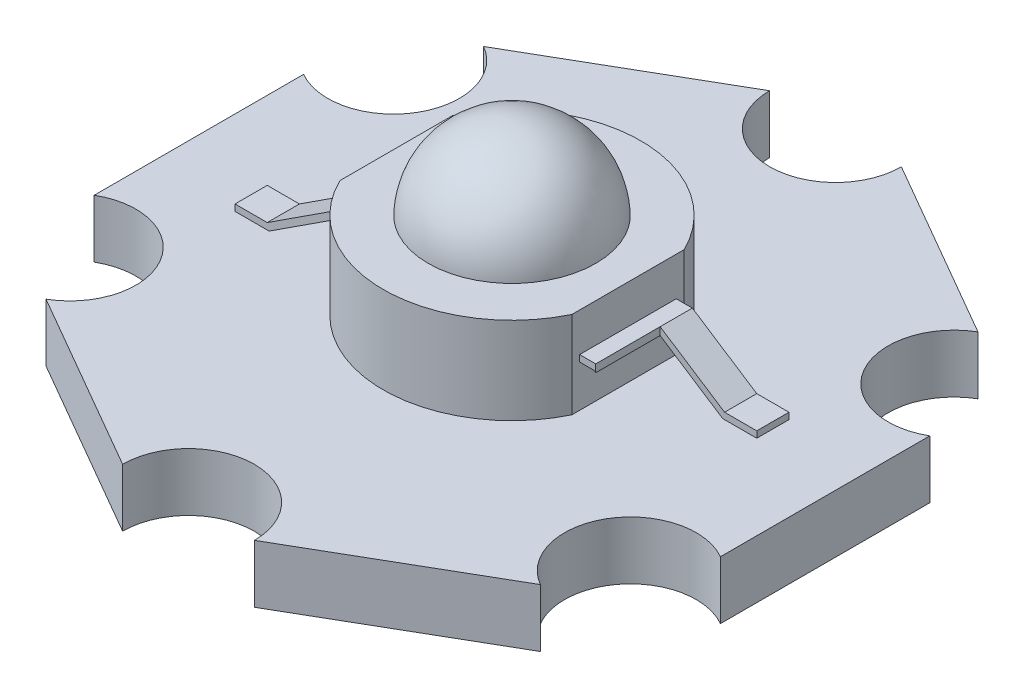
SolidWorks part; units mm, degrees
ref_plane "Front Plane" through (0, 0, 0) normal (0, 0, 1) x (1, 0, 0)
ref_plane "Top Plane" through (0, 0, 0) normal (0, 1, 0) x (1, 0, 0)
ref_plane "Right Plane" through (0, 0, 0) normal (1, 0, 0) x (0, 0, -1)
sketch "Sketch1" plane through (0, 0, 0) normal (0, 1, 0) x (1, 0, 0)
  line L0 (-10.25, 0) -> (0, 0) construction
  line L1 (0, 0) -> (10.25, 0) construction
  line L2 (-9.7211, 3.25) -> (-9.7211, 0)
  line L3 (-9.7211, 0) -> (-9.7211, -3.25)
  line L4 (0, 0) -> (0, 10.25) construction
  line L5 (0, 0) -> (0, -10.25) construction
  line L6 (-4.8606, 8.4187) -> (-7.6751, 6.7937)
  line L7 (-2.046, 10.0437) -> (-4.8606, 8.4187)
  line L8 (4.8606, 8.4187) -> (2.046, 10.0437)
  line L9 (7.6751, 6.7937) -> (4.8606, 8.4187)
  line L10 (9.7211, 0) -> (9.7211, 3.25)
  line L11 (9.7211, -3.25) -> (9.7211, 0)
  line L12 (4.8606, -8.4187) -> (7.6751, -6.7937)
  line L13 (2.046, -10.0437) -> (4.8606, -8.4187)
  line L14 (-4.8606, -8.4187) -> (-2.046, -10.0437)
  line L15 (-7.6751, -6.7937) -> (-4.8606, -8.4187)
  circle A0 centre (0, 0) radius 10.25 construction
  circle A1 centre (0, 0) radius 8 construction
  arc A2 (-9.7211, 3.25) -> (-7.6751, 6.7937) centre (-8.7001, 5.023) ccw
  arc A3 (-2.046, 10.0437) -> (2.046, 10.0437) centre (0, 10.046) ccw
  arc A4 (7.6751, 6.7937) -> (9.7211, 3.25) centre (8.7001, 5.023) ccw
  arc A5 (9.7211, -3.25) -> (7.6751, -6.7937) centre (8.7001, -5.023) ccw
  arc A6 (2.046, -10.0437) -> (-2.046, -10.0437) centre (0, -10.046) ccw
  arc A7 (-7.6751, -6.7937) -> (-9.7211, -3.25) centre (-8.7001, -5.023) ccw
  point P28 (0, 0)
  point P46 (0, 0)
  dimension "D1" = 20.5
  dimension "D2" = 16
  dimension "D3" = 6.5
  dimension "D4" = 6
  dimension "D5" = 6
extrude "Boss-Extrude1" add sketch "Sketch1" along normal blind 1.8
sketch "Sketch2" plane through (0, 1.8, 0) normal (0, 1, 0) x (1, 0, 0)
  circle A0 centre (0, 0) radius 4
  dimension "D1" = 8
extrude "Boss-Extrude2" add sketch "Sketch2" along normal blind 2.7
sketch "Sketch3" plane through (0, 4.5, 0) normal (0, 1, 0) x (1, 0, 0)
  line L0 (-3.6, 5.0619) -> (-3.6, -4.9568)
  line L1 (-3.6, -4.9568) -> (3.6, -4.9568)
  line L2 (3.6, -4.9568) -> (3.6, 5.2871)
  line L3 (3.6, 5.2871) -> (4.7694, 5.2871)
  line L4 (4.7694, 5.2871) -> (4.7694, -6.0544)
  line L5 (4.7694, -6.0544) -> (-4.6413, -6.0544)
  line L6 (-4.6413, -6.0544) -> (-4.6413, 5.0619)
  line L7 (-4.6413, 5.0619) -> (-3.6, 5.0619)
  line L8 (0, 0) -> (3.6, 0) construction
  line L9 (0, 0) -> (-3.6, 0) construction
  dimension "D1" = 7.2
extrude "Cut-Extrude1" cut sketch "Sketch3" against normal up to surface (2.7 mm away) up to face at (0, 1.8, 4)
sketch "Sketch4" plane through (0, 0, 0) normal (1, 0, 0) x (0, 0, -1)
  line L0 (0, 0) -> (0, 10.0744) construction
  line L1 (0, 7) -> (0, 4.5)
  line L2 (1.7436, 4.5) -> (-1.7436, 4.5) construction
  line L3 (0, 4.5) -> (2.6, 4.5)
  line L4 (4, 4.5) -> (1.7436, 4.5) construction
  line L5 (0, 7) -> (-1.2549, 7) construction
  arc A0 (0, 7) -> (2.6, 4.5) centre (0, 4.398) cw
  dimension "D2" = 7
  dimension "D1" = 5.2
revolve "Revolve1" add sketch "Sketch4" angle 360 about L0
sketch "Sketch5" plane through (0, 0, 0) normal (0, 0, 1) x (1, 0, 0)
  line L0 (3.6, 3.3) -> (3.6, 3.1)
  line L1 (3.6, 1.8) -> (3.6, 4.5) construction
  line L2 (3.6, 3.1) -> (4.0407, 3.1)
  line L3 (4.0407, 3.1) -> (6.0407, 1.8)
  line L4 (2.046, 1.8) -> (7.6751, 1.8) construction
  line L5 (6.0407, 1.8) -> (7.1, 1.8)
  line L6 (7.1, 1.8) -> (7.1, 2)
  line L7 (7.1, 2) -> (6.1, 2)
  line L8 (6.1, 2) -> (4.1, 3.3)
  line L9 (4.1, 3.3) -> (3.6, 3.3)
  line L10 (0, 0) -> (0, 9.0641) construction
  line L11 (-7.1, 1.8) -> (-7.1, 2)
  line L12 (-6.0407, 1.8) -> (-7.1, 1.8)
  line L13 (-7.1, 2) -> (-6.1, 2)
  line L14 (-6.1, 2) -> (-4.1, 3.3)
  line L15 (-4.0407, 3.1) -> (-6.0407, 1.8)
  line L16 (-3.6, 3.3) -> (-3.6, 3.1)
  line L17 (-4.1, 3.3) -> (-3.6, 3.3)
  line L18 (-3.6, 3.1) -> (-4.0407, 3.1)
  dimension "D1" = 3.5
  dimension "D2" = 0.5
  dimension "D3" = 0.2
  dimension "D4" = 0.2
  dimension "D5" = 0.2
  dimension "D6" = 1
  dimension "D7" = 1.5
extrude "Boss-Extrude3" add sketch "Sketch5" along normal blind 1.5 and the other way blind 1.5
sketch "Sketch6" plane through (0, 3.3, 0) normal (0, 1, 0) x (1, 0, 0)
  line L0 (-4.1, 1.5) -> (-4.1, -0.5)
  line L1 (-4.1, 1.5) -> (-4.1, -1.5) construction
  line L2 (-4.1, -0.5) -> (-7.1, -0.5)
  line L3 (-7.1, -0.5) -> (-7.1, 1.5)
  line L4 (-7.1, 1.5) -> (-4.1, 1.5)
  line L5 (4.1, 0.5) -> (7.1, 0.5)
  line L6 (4.1, 1.5) -> (4.1, -1.5) construction
  line L7 (7.1, 1.5) -> (7.1, -1.5) construction
  line L8 (7.1, 0.5) -> (7.1, -1.5)
  line L9 (7.1, -1.5) -> (4.1, -1.5)
  line L10 (4.1, -1.5) -> (4.1, 0.5)
  line L11 (-7.1, 1.5) -> (-7.1, -1.5) construction
  dimension "D1" = 1
extrude "Cut-Extrude2" cut sketch "Sketch6" against normal up to surface (1.5 mm away) up to face at (-6.5704, 1.8, 0)
